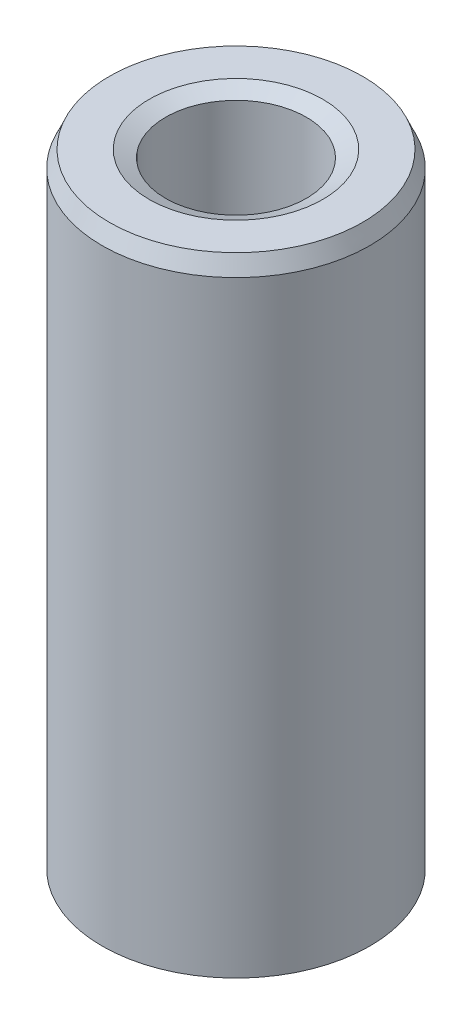
SolidWorks part; units mm, degrees
ref_plane "Front Plane" through (0, 0, 0) normal (0, 0, 1) x (1, 0, 0)
ref_plane "Top Plane" through (0, 0, 0) normal (0, 1, 0) x (1, 0, 0)
ref_plane "Right Plane" through (0, 0, 0) normal (1, 0, 0) x (0, 0, -1)
sketch "Sketch1" plane through (0, 0, 0) normal (0, 1, 0) x (1, 0, 0)
  circle A0 centre (0, 0) radius 25
  dimension "SLEEVE_OD" = 50
extrude "Boss-Extrude1" add sketch "Sketch1" along normal blind 117.6856
sketch "Sketch2" plane through (0, 0, 0) normal (0, 1, 0) x (1, 0, 0)
  circle A0 centre (0, 0) radius 13.1403
  dimension "BORE_D" = 26.2807
extrude "Cut-Extrude1" cut sketch "Sketch2" along normal through all
chamfer "Chamfer1" distance 3.0684 angle 23.983 4 edges at (0, 117.6856, 13.1403) (0, 0, 13.1403) (0, 0, 25) (0, 117.6856, 25) first distance on face at (0, 117.6856, 13.1403) first distance on face at (0, 0, 13.1403) first distance on face at (0, 117.6856, 25)
